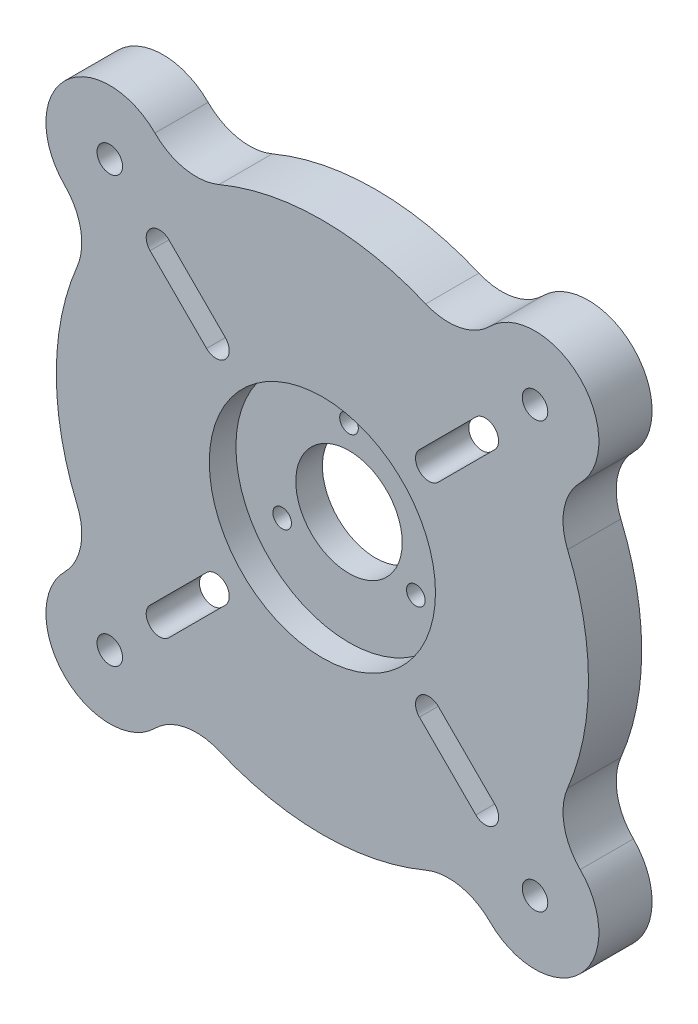
SolidWorks part; units mm, degrees
material "Cast Alloy Steel"
ref_plane "Front" through (0, 0, 0) normal (0, 0, 1) x (1, 0, 0)
ref_plane "Top" through (0, 0, 0) normal (0, 1, 0) x (1, 0, 0)
ref_plane "Right" through (0, 0, 0) normal (1, 0, 0) x (0, 0, -1)
sketch "Sketch1" plane through (0, 0, 0) normal (0, 0, 1) x (1, 0, 0)
  line L0 (39.9515, 39.9515) -> (-39.9515, -39.9515) construction
  line L1 (48.4368, 31.4663) -> (-31.4663, -48.4368) construction
  line L2 (31.4663, 48.4368) -> (-48.4368, -31.4663) construction
  line L3 (0, 0) -> (0, 50) construction
  line L4 (39.9515, -39.9515) -> (-39.9515, 39.9515) construction
  line L5 (31.4663, -48.4368) -> (-48.4368, 31.4663) construction
  line L6 (48.4368, -31.4663) -> (-31.4663, 48.4368) construction
  line L7 (20, 20) -> (30.6066, 30.6066) construction
  line L8 (18.2322, 21.7678) -> (28.8388, 32.3744)
  line L9 (21.7678, 18.2322) -> (32.3744, 28.8388)
  line L10 (20, -20) -> (30.6066, -30.6066) construction
  line L11 (21.7678, -18.2322) -> (32.3744, -28.8388)
  line L12 (18.2322, -21.7678) -> (28.8388, -32.3744)
  line L13 (-20, -20) -> (-30.6066, -30.6066) construction
  line L14 (-18.2322, -21.7678) -> (-28.8388, -32.3744)
  line L15 (-21.7678, -18.2322) -> (-32.3744, -28.8388)
  line L16 (-20, 20) -> (-30.6066, 30.6066) construction
  line L17 (-21.7678, 18.2322) -> (-32.3744, 28.8388)
  line L18 (-18.2322, 21.7678) -> (-28.8388, 32.3744)
  circle A0 centre (0, 0) radius 50
  arc A1 (48.4368, 31.4663) -> (31.4663, 48.4368) centre (39.9515, 39.9515) ccw construction
  arc A2 (-48.4368, -31.4663) -> (-31.4663, -48.4368) centre (-39.9515, -39.9515) ccw construction
  arc A3 (31.4663, -48.4368) -> (48.4368, -31.4663) centre (39.9515, -39.9515) ccw construction
  arc A4 (-31.4663, 48.4368) -> (-48.4368, 31.4663) centre (-39.9515, 39.9515) ccw construction
  arc A5 (31.4663, 48.4368) -> (19.4135, 46.0773) centre (23.6858, 56.2173) cw
  arc A6 (48.4368, 31.4663) -> (46.0773, 19.4135) centre (56.2173, 23.6858) ccw
  arc A7 (31.4663, 48.4368) -> (48.4368, 31.4663) centre (39.9515, 39.9515) cw
  circle A8 centre (39.9515, 39.9515) radius 2.4
  arc A9 (18.2322, 21.7678) -> (21.7678, 18.2322) centre (20, 20) ccw
  arc A10 (32.3744, 28.8388) -> (28.8388, 32.3744) centre (30.6066, 30.6066) ccw
  arc A11 (48.4368, -31.4663) -> (46.0773, -19.4135) centre (56.2173, -23.6858) cw
  arc A12 (48.4368, -31.4663) -> (31.4663, -48.4368) centre (39.9515, -39.9515) cw
  arc A13 (31.4663, -48.4368) -> (19.4135, -46.0773) centre (23.6858, -56.2173) ccw
  circle A14 centre (39.9515, -39.9515) radius 2.4
  arc A15 (21.7678, -18.2322) -> (18.2322, -21.7678) centre (20, -20) ccw
  arc A16 (28.8388, -32.3744) -> (32.3744, -28.8388) centre (30.6066, -30.6066) ccw
  arc A17 (-31.4663, -48.4368) -> (-19.4135, -46.0773) centre (-23.6858, -56.2173) cw
  arc A18 (-31.4663, -48.4368) -> (-48.4368, -31.4663) centre (-39.9515, -39.9515) cw
  arc A19 (-48.4368, -31.4663) -> (-46.0773, -19.4135) centre (-56.2173, -23.6858) ccw
  circle A20 centre (-39.9515, -39.9515) radius 2.4
  arc A21 (-18.2322, -21.7678) -> (-21.7678, -18.2322) centre (-20, -20) ccw
  arc A22 (-32.3744, -28.8388) -> (-28.8388, -32.3744) centre (-30.6066, -30.6066) ccw
  arc A23 (-48.4368, 31.4663) -> (-46.0773, 19.4135) centre (-56.2173, 23.6858) cw
  arc A24 (-48.4368, 31.4663) -> (-31.4663, 48.4368) centre (-39.9515, 39.9515) cw
  arc A25 (-31.4663, 48.4368) -> (-19.4135, 46.0773) centre (-23.6858, 56.2173) ccw
  circle A26 centre (-39.9515, 39.9515) radius 2.4
  arc A27 (-21.7678, 18.2322) -> (-18.2322, 21.7678) centre (-20, 20) ccw
  arc A28 (-28.8388, 32.3744) -> (-32.3744, 28.8388) centre (-30.6066, 30.6066) ccw
  point P5 (0, 0)
  point P13 (0, 0)
  point P28 (25.3033, 25.3033)
  point P46 (25.3033, -25.3033)
  point P61 (-25.3033, -25.3033)
  point P76 (-25.3033, 25.3033)
  point P81 (0, 0)
  dimension "D1" = 100
  dimension "D2" = 12
  dimension "D5" = 4.8
  dimension "D6" = 2.5
  dimension "D3" = 113
  dimension "D4" = 45
  dimension "D7" = 15
  dimension "D8" = 20
  dimension "D9" = 4
extrude "Boss-Extrude1" add sketch "Sketch1" along normal blind 10 contours A19 A18 A17 A0 A20 | A0 A28 L18 A27 L17 A22 L15 A21 L14 A16 L12 A15 L11 A10 L9 A9 L8 | A25 A24 A23 A0 A26 | A7 A5 A0 A6 A8 | A13 A12 A11 A0 A14 region at (0, 0, 0) region at (35.6807, 35.6807, 0) region at (44.9674, -25.8881, 0) region at (-35.6807, 35.6807, 0) region at (-25.8881, -44.9674, 0)
sketch "Sketch2" plane through (0, 0, 10) normal (0, 0, 1) x (1, 0, 0)
  circle A0 centre (0, 0) radius 21.25
  circle A1 centre (0, 14.5) radius 1.75
  circle A2 centre (12.5574, -7.25) radius 1.75
  circle A3 centre (-12.5574, -7.25) radius 1.75
  point P12 (0, 0)
  dimension "D1" = 42.5
  dimension "D2" = 3.5
  dimension "D3" = 14.5
  dimension "D5" = 35.8794
  dimension "D6" = 60.9942
  dimension "D4" = 3
extrude "Cut-Extrude1" cut sketch "Sketch2" against normal blind 5 contours A0
extrude "Cut-Extrude2" cut sketch "Sketch2<3>" against normal through all contours A1 | A3 | A2
sketch "Sketch2<3>" plane through (0, 0, 10) normal (0, 0, 1) x (1, 0, 0) same geometry as "Sketch2"
sketch "Sketch3" plane through (0, 0, 5) normal (0, 0, 1) x (1, 0, 0)
  circle A0 centre (0, 0) radius 10
  dimension "D1" = 20
extrude "Cut-Extrude3" cut sketch "Sketch3" against normal through all
